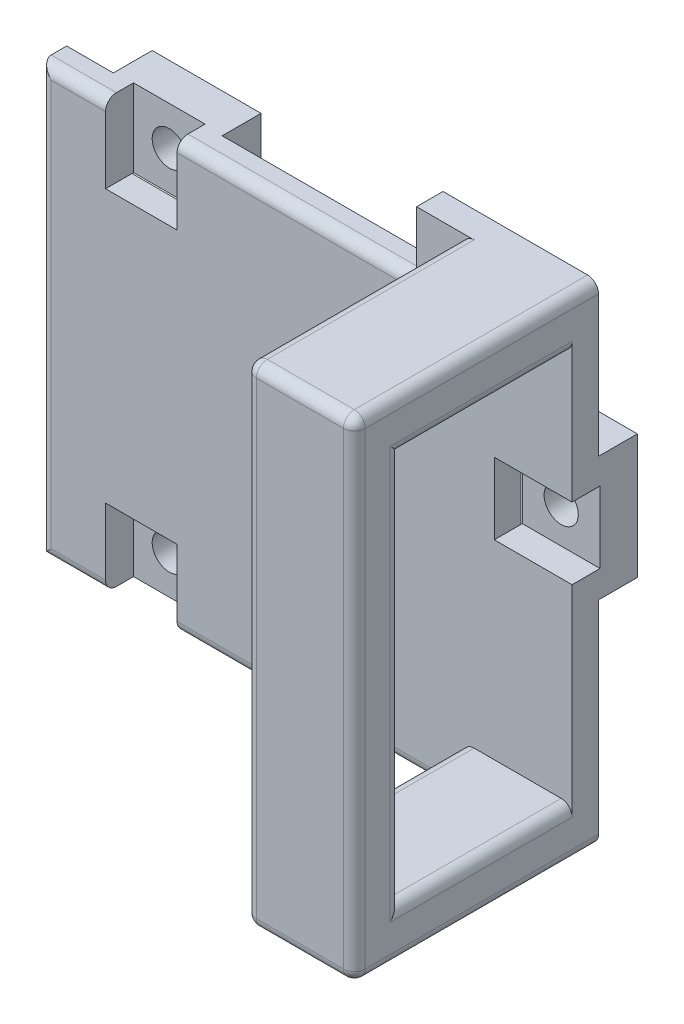
SolidWorks part; units mm, degrees
ref_plane "Płaszczyzna przednia" through (0, 0, 0) normal (0, 0, 1) x (1, 0, 0)
ref_plane "Płaszczyzna górna" through (0, 0, 0) normal (0, 1, 0) x (1, 0, 0)
ref_plane "Płaszczyzna prawa" through (0, 0, 0) normal (1, 0, 0) x (0, 0, -1)
sketch "Szkic1" plane through (0, 0, 158.8329) normal (0, 0, 1) x (1, 0, 0)
  line L0 (-31.9233, -22.4743) -> (2.0767, -22.4743) construction
  line L1 (-17.2684, -17.4743) -> (-10.2684, -17.4743)
  line L2 (-17.2684, -17.4743) -> (-17.2684, -22.4743)
  line L3 (-17.2684, -22.4743) -> (-10.2684, -22.4743)
  line L4 (-10.2684, -17.4743) -> (-10.2684, -22.4743)
  line L5 (-17.2684, -17.4743) -> (-10.2684, -22.4743) construction
  line L6 (-17.2684, -22.4743) -> (-10.2684, -17.4743) construction
  line L12 (13.9316, -0.7243) -> (8.9316, -0.7243)
  line L13 (13.9316, -0.7243) -> (13.9316, -8.7243)
  line L14 (-17.2684, 0.0257) -> (-10.2684, 0.0257)
  line L15 (-17.2684, 0.0257) -> (-17.2684, 5.0257)
  line L16 (-17.2684, 5.0257) -> (-10.2684, 5.0257)
  line L17 (-10.2684, 0.0257) -> (-10.2684, 5.0257)
  line L18 (-17.2684, 0.0257) -> (-10.2684, 5.0257) construction
  line L19 (-17.2684, 5.0257) -> (-10.2684, 0.0257) construction
  line L20 (13.9316, -8.7243) -> (8.9316, -8.7243)
  line L21 (8.9316, -0.7243) -> (8.9316, -8.7243)
  circle A3 centre (11.4316, -4.7243) radius 1.1
  circle A4 centre (-13.7684, -19.9743) radius 1.1
  circle A5 centre (-13.7684, 2.5257) radius 1.1
  dimension "D4" = 2.2
  dimension "D13" = 2.2
  dimension "D14" = 2.2
  dimension "D1" = 22.5
  dimension "D2" = 25.2
  dimension "D3" = 2.5
  dimension "D5" = 25.2
  dimension "D6" = 15.25
  dimension "D7" = 2.5
  dimension "D8" = 3.5
  dimension "D9" = 2.5
  dimension "D10" = 2.5
  dimension "D11" = 4
  dimension "D12" = 4
  dimension "D15" = 3.5
extrude "Dodanie-wyciągnięcie1" add sketch "Szkic1" along normal blind 2.5
sketch "Szkic2" plane through (0, 0, 161.3329) normal (0, 0, 1) x (1, 0, 0)
  line L11 (-20.2684, 5.0257) -> (13.9316, 5.0257)
  line L18 (13.9316, -22.4743) -> (-20.2684, -22.4743)
  line L20 (-10.2684, 5.0257) -> (-17.2684, 5.0257) construction
  line L21 (-20.2684, 5.0257) -> (-20.2684, -22.4743)
  line L22 (-17.2684, 5.0257) -> (-17.2684, 0.0257) construction
  line L23 (13.9316, 5.0257) -> (13.9316, -22.4743)
  line L24 (13.9316, -8.7243) -> (13.9316, -0.7243) construction
  line L25 (-17.2684, -22.4743) -> (-10.2684, -22.4743) construction
  circle A9 centre (11.4316, -4.7243) radius 1.1
  circle A10 centre (-13.7684, -19.9743) radius 1.1
  circle A11 centre (-13.7684, 2.5257) radius 1.1
  dimension "D1" = 3
extrude "Dodanie-wyciągnięcie2" add sketch "Szkic2" along normal blind 1.7
sketch "Szkic7" plane through (0, 5.0257, 0) normal (0, 1, 0) x (1, 0, 0)
  line L0 (13.9316, -163.0329) -> (-20.2684, -163.0329) construction
  line L1 (13.9316, -163.0329) -> (3.9316, -163.0329)
  line L2 (13.9316, -163.0329) -> (13.9316, -161.3329)
  line L3 (13.9316, -161.3329) -> (3.9316, -161.3329)
  line L4 (3.9316, -163.0329) -> (3.9316, -161.3329)
  line L5 (13.9316, -161.3329) -> (-10.2684, -161.3329) construction
  dimension "D1" = 10
extrude "Dodanie-wyciągnięcie3" add sketch "Szkic7" along normal blind 4
sketch "Sketch1" plane through (0, 0, 163.0329) normal (0, 0, 1) x (1, 0, 0)
  line L1 (6.9316, -22.4743) -> (13.9316, -22.4743)
  line L2 (6.9316, -22.4743) -> (6.9316, -19.2743)
  line L3 (6.9316, -19.2743) -> (13.9316, -19.2743)
  line L4 (13.9316, -22.4743) -> (13.9316, -19.2743)
  line L5 (3.9316, 9.0257) -> (13.9316, 9.0257) construction
  line L6 (6.9316, 9.0257) -> (13.9316, 9.0257)
  line L7 (6.9316, 9.0257) -> (6.9316, 5.8257)
  line L8 (6.9316, 5.8257) -> (13.9316, 5.8257)
  line L9 (13.9316, 9.0257) -> (13.9316, 5.8257)
  point P4 (13.9316, 9.0257)
  point P5 (13.9316, -22.4743)
  point P12 (13.9316, 9.0257)
  point P13 (6.9316, 8.4748)
  point P14 (0, 0)
  dimension "D1" = 7
  dimension "D3" = 3.2
  dimension "D4" = 3.2
extrude "Boss-Extrude2" add sketch "Sketch1" along normal blind 11
sketch "Sketch2" plane through (0, 0, 174.0329) normal (0, 0, 1) x (1, 0, 0)
  line L1 (6.9316, -22.4743) -> (13.9316, -22.4743)
  line L2 (6.9316, -22.4743) -> (6.9316, 9.0257)
  line L3 (6.9316, 9.0257) -> (13.9316, 9.0257)
  line L4 (13.9316, -22.4743) -> (13.9316, 9.0257)
  line L5 (6.9316, -22.4743) -> (13.9316, -22.4743) construction
  point P4 (13.9316, 9.0257)
extrude "Boss-Extrude3" add sketch "Sketch2" along normal blind 3
sketch "Sketch3" plane through (0, 0, 163.0329) normal (0, 0, 1) x (1, 0, 0)
  line L0 (-20.2684, -22.4743) -> (6.9316, -22.4743) construction
  line L1 (-16.0684, -22.4743) -> (-11.4684, -22.4743)
  line L2 (-16.0684, -22.4743) -> (-16.0684, -17.4743)
  line L3 (-16.0684, -17.4743) -> (-11.4684, -17.4743)
  line L4 (-11.4684, -22.4743) -> (-11.4684, -17.4743)
  line L5 (3.9316, 5.0257) -> (-20.2684, 5.0257) construction
  line L6 (-16.0684, 5.0257) -> (-11.4684, 5.0257)
  line L7 (-16.0684, 5.0257) -> (-16.0684, 0.0257)
  line L8 (-16.0684, 0.0257) -> (-11.4684, 0.0257)
  line L9 (-11.4684, 5.0257) -> (-11.4684, 0.0257)
  line L11 (8.9316, -7.0243) -> (13.9316, -7.0243)
  line L12 (8.9316, -7.0243) -> (8.9316, -2.4243)
  line L13 (8.9316, -2.4243) -> (13.9316, -2.4243)
  line L14 (13.9316, -7.0243) -> (13.9316, -2.4243)
  line L15 (13.9316, -22.4743) -> (13.9316, 9.0257) construction
  circle A0 centre (-13.7684, -19.9743) radius 1.1 construction
  circle A1 centre (-13.7684, 2.5257) radius 1.1 construction
  circle A2 centre (11.4316, -4.7243) radius 1.1 construction
  circle A3 centre (-13.7684, -19.9743) radius 1.1
  circle A4 centre (-13.7684, 2.5257) radius 1.1
  circle A5 centre (11.4316, -4.7243) radius 1.1
  dimension "D1" = 2.3
  dimension "D2" = 2.3
  dimension "D3" = 2.5
  dimension "D4" = 2.5
  dimension "D5" = 2.3
  dimension "D6" = 2.3
  dimension "D7" = 2.3
  dimension "D8" = 2.3
  dimension "D9" = 2.5
extrude "Cut-Extrude1" cut sketch "Sketch3" against normal blind 1.8
fillet "Fillet1" radius 0.7 12 edges at (6.9316, -19.2743, 168.5329) (6.9316, -6.7243, 174.0329) (6.9316, 5.8257, 168.5329) (13.9316, -19.2743, 168.5329) (13.9316, -6.7243, 174.0329) (13.9316, 5.8257, 168.5329) (13.9316, 9.0257, 169.1829) (10.4316, 9.0257, 177.0329) (6.9316, 9.0257, 170.0329) (13.9316, -22.4743, 169.1829) (10.4316, -22.4743, 177.0329) (6.9316, -22.4743, 170.0329)
fillet "Fillet2" radius 0.7 6 edges at (13.7266, -22.2692, 176.8279) (13.7266, 8.8207, 176.8279) (7.1366, 8.8207, 176.8279) (7.1366, -22.2692, 176.8279) (13.9316, -6.7243, 177.0329) (6.9316, -6.7243, 177.0329)
fillet "Fillet3" radius 0.7 5 edges at (-1.9184, -22.4743, 163.0329) (-3.7684, 5.0257, 163.0329) (-18.1684, 5.0257, 163.0329) (-18.1684, -22.4743, 163.0329) (-20.2684, -8.7243, 163.0329)
